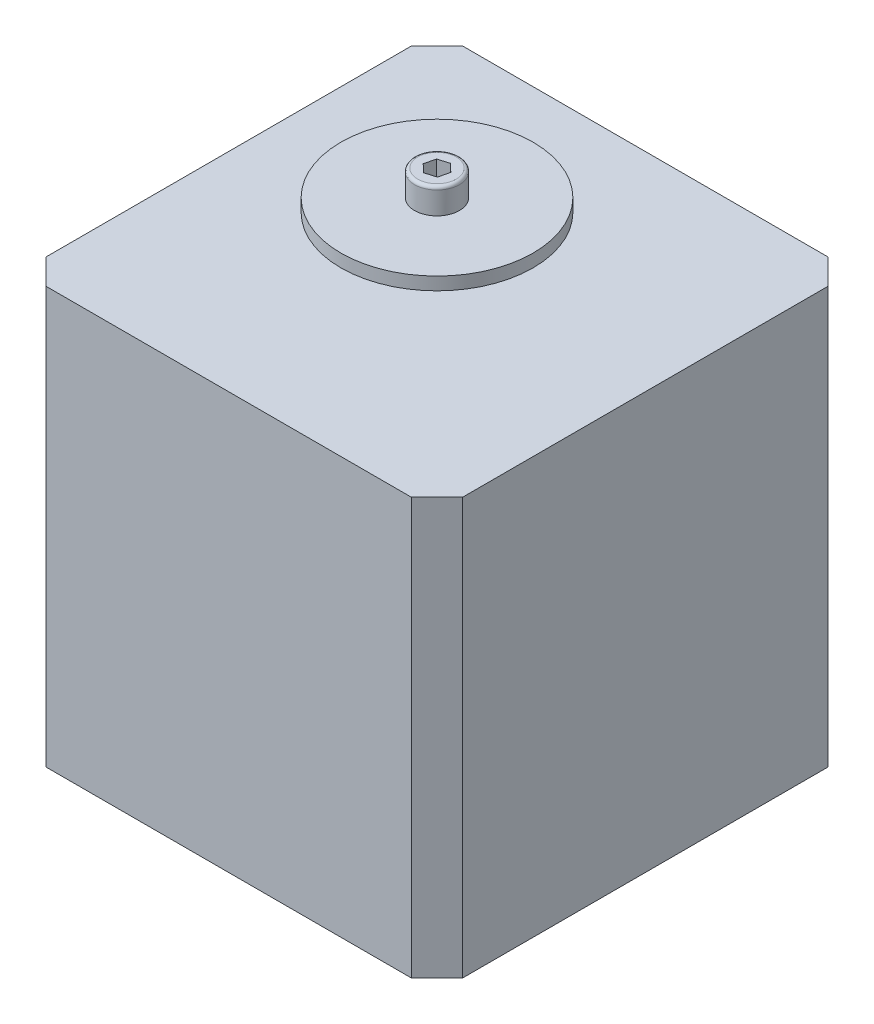
SolidWorks part; units mm, degrees
ref_plane "Front" through (0, 0, 0) normal (0, 0, 1) x (1, 0, 0)
ref_plane "Top" through (0, 0, 0) normal (0, 1, 0) x (1, 0, 0)
ref_plane "Right" through (0, 0, 0) normal (1, 0, 0) x (0, 0, -1)
sketch "Esquisse3" plane through (0, 0, 0) normal (0, 1, 0) x (1, 0, 0)
  line L1 (-32.5, -32.5) -> (32.5, -32.5)
  line L2 (-32.5, -32.5) -> (-32.5, 32.5)
  line L3 (-32.5, 32.5) -> (32.5, 32.5)
  line L4 (32.5, -32.5) -> (32.5, 32.5)
  line L5 (0, 32.5) -> (0, -32.5) construction
  line L6 (-32.5, 0) -> (32.5, 0) construction
  line L7 (-30, -30) -> (30, -30) construction
  line L8 (-30, -30) -> (-30, 30) construction
  line L9 (-30, 30) -> (30, 30) construction
  line L10 (30, -30) -> (30, 30) construction
  line L11 (0, 30) -> (0, -30) construction
  line L12 (-30, 0) -> (30, 0) construction
  point P0 (0, 0)
  point P4 (0, 0)
  dimension "D1" = 65
  dimension "D2" = 60
extrude "Boss.-Extru.3" add sketch "Esquisse3" along normal blind 65 separate body
chamfer "Chanfrein1" distance 4 angle 45 4 edges at (32.5, 32.5, 32.5) (-32.5, 32.5, 32.5) (32.5, 32.5, -32.5) (-32.5, 32.5, -32.5)
sketch "Esquisse4" plane through (0, 0, 0) normal (0, 0, 1) x (1, 0, 0)
  line L0 (0, 65) -> (0, 79)
  line L2 (3.5, 75) -> (15, 75)
  line L3 (15, 75) -> (15, 73)
  line L4 (15, 73) -> (3, 73)
  line L5 (3, 73) -> (3, 65)
  line L6 (3, 65) -> (0, 65)
  line L7 (0, 79) -> (0, 82.5) construction
  line L8 (-28.5, 65) -> (28.5, 65) construction
  line L9 (3.5, 75) -> (3.5, 79)
  line L10 (3.5, 79) -> (0, 79)
  dimension "D1" = 6
  dimension "D2" = 2
  dimension "D3" = 8
  dimension "D4" = 30
  dimension "D5" = 7
  dimension "D6" = 4
revolve "Révolution1" add sketch "Esquisse4" angle 360 about L7
sketch "Esquisse5" plane through (0, 79, 0) normal (0, 1, 0) x (1, 0, 0)
  line L1 (1.262, -1.1863) -> (1.6584, 0.4998)
  line L2 (1.6584, 0.4998) -> (0.3964, 1.6861)
  line L3 (0.3964, 1.6861) -> (-1.262, 1.1863)
  line L4 (-1.262, 1.1863) -> (-1.6584, -0.4998)
  line L5 (-1.6584, -0.4998) -> (-0.3964, -1.6861)
  line L6 (-0.3964, -1.6861) -> (1.262, -1.1863)
  circle A0 centre (0, 0) radius 1.5 construction
  dimension "D1" = 3
extrude "Enlèv. mat.-Extru.1" cut sketch "Esquisse5" against normal blind 2.5
fillet "Congé1" radius 0.5 1 edges at (0, 79, -3.5)
